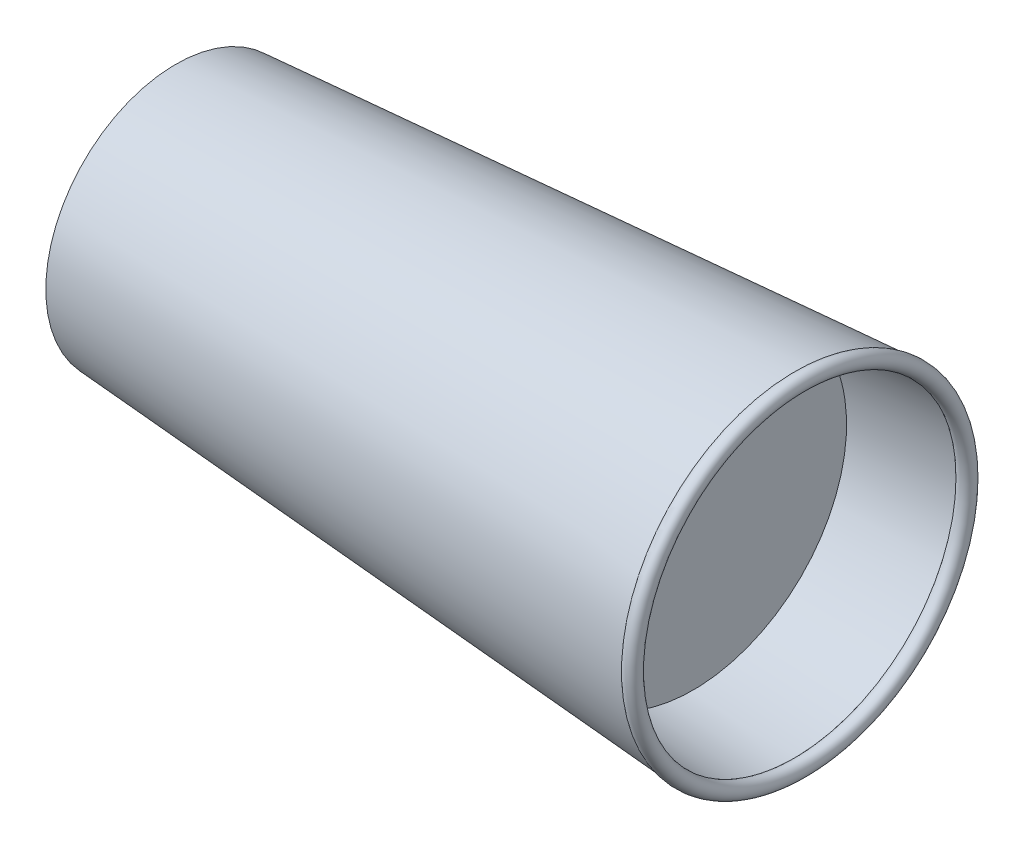
SolidWorks part; units mm, degrees
other "Water"
material "PTFE (general)"
ref_plane "Front Plane" through (0, 0, 0) normal (0, 0, 1) x (1, 0, 0)
ref_plane "Top Plane" through (0, 0, 0) normal (0, 1, 0) x (1, 0, 0)
ref_plane "Right Plane" through (0, 0, 0) normal (1, 0, 0) x (0, 0, -1)
sketch "Sketch1" plane through (0, 0, 0) normal (1, 0, 0) x (0, 0, -1)
  circle A0 centre (0, 0) radius 31.75
  dimension "D1" = 63.5
extrude "Boss-Extrude1" add sketch "Sketch1" along normal blind 152.4
draft "Draft1" type of draft neutral plane draft angle 4 faces to draft 1 face at (152.4, 0, -31.75) neutral plane through (0, 0, 0) neutral plane normal (-1, 0, 0) parameters "D1"=4
sketch "Sketch3" plane through (0, 0, 0) normal (-1, 0, 0) x (0, 0, 1)
  circle A2 centre (0, 0) radius 29.21
  circle A3 centre (0, 0) radius 29.21
  dimension "D1" = 2.54
extrude "Cut-Extrude1" cut sketch "Sketch3" against normal blind 3.175
shell "Shell2" thickness 2.54 removed face at (152.4, 0, -42.4068)
ref_axis "Axis1" through (152.4, 0, 0) along (-1, 0, 0)
sketch "Sketch4" plane through (0, 0, 0) normal (0, 1, 0) x (1, 0, 0)
  line L0 (152.4, -42.4068) -> (152.4, 42.4068) construction
  circle A0 centre (152.4, 40.8522) radius 1.905
  point P0 (152.4, 40.8522)
  dimension "D1" = 3.81
revolve "Revolve1" add sketch "Sketch4" angle 360 about axis through (152.4, 0, 0) along (-1, 0, 0) region at (152.4, 0, -40.8522)
ref_plane "Plane1" through (126.365, 0, 0) normal (1, 0, 0) x (0, 0, -1)
sketch "Sketch5" plane through (126.365, 0, 0) normal (1, 0, 0) x (0, 0, -1)
  circle A0 centre (0, 0) radius 37.4797
sketch "Sketch6" plane through (5.715, 0, 0) normal (1, 0, 0) x (0, 0, -1)
  circle A1 centre (0, 0) radius 29.6034
  circle A2 centre (0, 0) radius 29.6034
  dimension "D1" = 0
loft "Loft1" add profiles "Sketch6", "Sketch5" connector at (5.715, 9.1303, 28.1603) connector at (126.365, -16.6999, 33.5535)
ref_plane "Plane2" through (0, 120.65, 0) normal (0, 1, 0) x (1, 0, 0)
